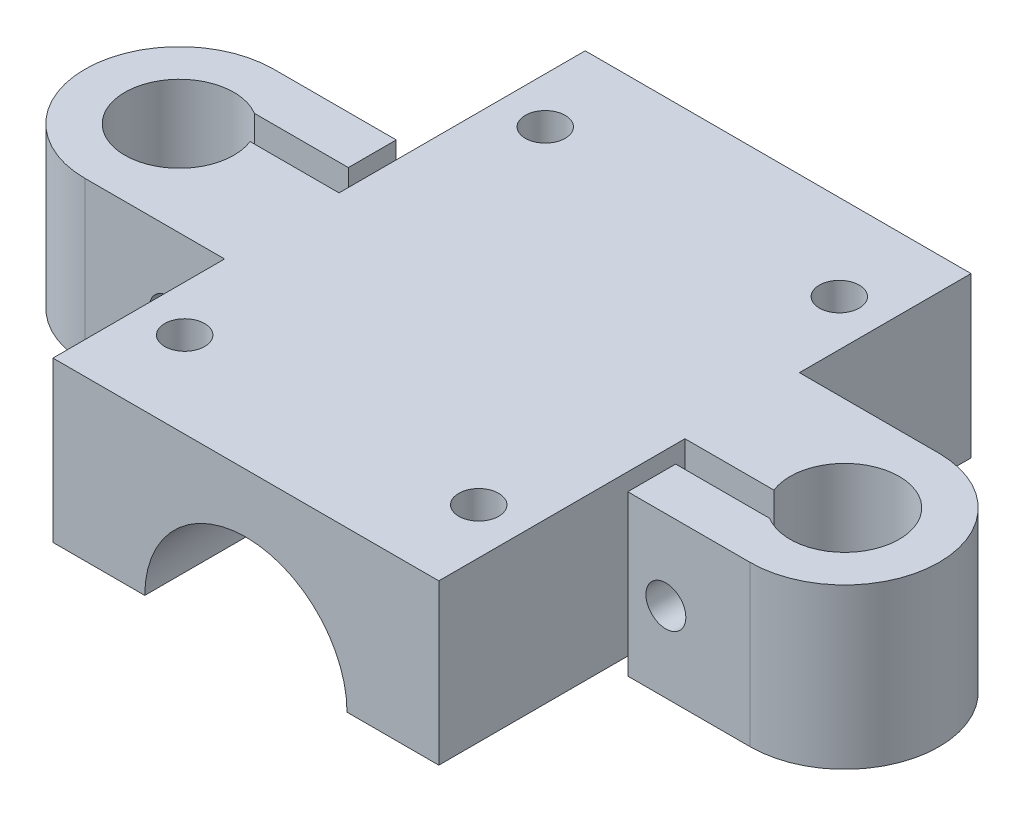
SolidWorks part; units mm, degrees
ref_plane "Front Plane" through (0, 0, 0) normal (1, 0, 0) x (0, 1, 0)
ref_plane "Top Plane" through (0, 0, 0) normal (0, 0, 1) x (0, 1, 0)
ref_plane "Right Plane" through (0, 0, 0) normal (0, 1, 0) x (-1, 0, 0)
sketch "Sketch1" plane through (0, 0, 0) normal (0, 0, 1) x (0, 1, 0)
  line L0 (0, -6.9) -> (0, -14.5) construction
  line L1 (0, 0) -> (12, 0)
  line L2 (0, 0) -> (0, -6.9)
  line L3 (0, -29) -> (12, -29)
  line L4 (12, 0) -> (12, -29)
  line L5 (6, -29) -> (6, 0) construction
  line L6 (0, -14.5) -> (12, -14.5) construction
  line L7 (0, -22.1) -> (0, -29)
  line L8 (0, -14.5) -> (0, -22.1) construction
  arc A0 (0, -22.1) -> (0, -6.9) centre (0, -14.5) ccw
  arc A1 (0, -6.9) -> (0, -22.1) centre (0, -14.5) ccw construction
  point P428 (6, -14.5)
  dimension "D3" = 15.2
  dimension "D1" = 29
  dimension "D2" = 12
extrude "Boss-Extrude1" add sketch "Sketch1" along normal blind 20 and the other way blind 20 contours A0 L7 L3 L4 L1 L2 region at (0.3138, 6, 0)
sketch "Sketch3" plane through (0, 12, 0) normal (0, 1, 0) x (-1, 0, 0)
  line L0 (0, 0) -> (-29, 0) construction
  line L1 (0, -20) -> (0, 20) construction
  line L2 (-29, -20) -> (-29, 20) construction
  line L3 (10.5, 0) -> (-39.5, 0) construction
  line L4 (10.5, -7.1) -> (-39.5, -7.1)
  line L5 (10.5, 7.1) -> (-39.5, 7.1)
  line L6 (-14.5, 20) -> (-14.5, -20) construction
  line L7 (0, 20) -> (-29, 20) construction
  line L8 (0, -20) -> (-29, -20) construction
  line L9 (1.3, -7.1) -> (1.3, -3.5)
  line L10 (1.3, -3.5) -> (8.3646, -3.5)
  line L11 (6.6842, -1.5) -> (0, -1.5)
  line L12 (0, -1.5) -> (0, -7.1)
  line L13 (0, -7.1) -> (1.3, -7.1)
  line L14 (-30.3, 7.1) -> (-30.3, 3.5)
  line L15 (-30.3, 3.5) -> (-37.3646, 3.5)
  line L16 (-35.6842, 1.5) -> (-29, 1.5)
  line L17 (-29, 1.5) -> (-29, 7.1)
  line L18 (-29, 7.1) -> (-30.3, 7.1)
  arc A0 (10.5, -7.1) -> (10.5, 7.1) centre (10.5, 0) ccw
  arc A1 (-39.5, 7.1) -> (-39.5, -7.1) centre (-39.5, 0) ccw
  arc A2 (-37.3646, 3.5) -> (-35.6842, 1.5) centre (-39.5, 0) ccw
  arc A3 (8.3646, -3.5) -> (6.6842, -1.5) centre (10.5, 0) ccw
  arc A4 (6.6842, -1.5) -> (8.3646, -3.5) centre (10.5, 0) ccw construction
  arc A5 (-35.6842, 1.5) -> (-37.3646, 3.5) centre (-39.5, 0) ccw construction
  point P9 (-14.5, 0)
  point P22 (-14.5, 0)
  line M6 (0, -20) -> (0, 20)
  line M8 (-29, 20) -> (-29, -20)
  dimension "D3" = 8.2
  dimension "D4" = 50
  dimension "D5" = 2
  dimension "D7" = 1.5
  dimension "D8" = 1.3
  dimension "D9" = 2
  dimension "D10" = 1.5
extrude "Boss-Extrude2" add sketch "Sketch3" against normal up to surface (12 mm away) contours A3 L10 L9 L4 A0 L5 L11 M6 | A2 L15 L14 L5 A1 L4 L16 M8 region at (-5.9, 12, -6.8739) region at (34.25, 12, -6.8739) up to face at (3.45, 0, 0)
sketch "Sketch4" plane through (0, 0, -1.5) normal (0, 0, -1) x (1, 0, 0)
  line L0 (-6.6842, -6) -> (0, -6) construction
  line L1 (-6.6842, 0) -> (-6.6842, -12) construction
  circle A0 centre (-4.1642, -6) radius 1.5
  dimension "screw_hole" = 3
  dimension "D1" = 2.52
extrude "Cut-Extrude1" cut sketch "Sketch4" against normal through all and the other way through all contours A0 L0 | L0 A0 region at (-4.1642, 5.3634, -1.5) region at (-4.1642, 6.6366, -1.5)
sketch "Sketch5" plane through (0, 0, 1.5) normal (0, 0, 1) x (1, 0, 0)
  line L0 (35.6842, 6) -> (29, 6) construction
  line L1 (35.6842, 0) -> (35.6842, 12) construction
  line L2 (29, 0) -> (29, 12) construction
  circle A0 centre (33.1642, 6) radius 1.5
  dimension "D2" = 2.52
extrude "Cut-Extrude2" cut sketch "Sketch5" against normal through all and the other way through all contours L0 A0 | A0 L0 region at (33.1642, 5.3634, 1.5) region at (33.1642, 6.6366, 1.5)
sketch "Sketch7" plane through (0, 0, 0) normal (0, -1, 0) x (1, 0, 0)
  line L0 (0, 20) -> (6.9, 7.1) construction
  line L1 (6.9, -20) -> (6.9, 20) construction
  line L2 (0, 7.1) -> (6.9, 20) construction
  line L3 (29, -7.1) -> (22.1, -20) construction
  line L4 (29, -20) -> (22.1, -7.1) construction
  line L5 (22.1, -20) -> (22.1, 20) construction
  line L6 (0, -20) -> (6.9, -7.1) construction
  line L7 (6.9, -20) -> (0, -7.1) construction
  line L9 (22.1, 20) -> (29, 7.1) construction
  line L10 (29, 1.5) -> (29, 20) construction
  line L11 (29, 20) -> (22.1, 7.1) construction
  line L12 (0, -20) -> (0, -1.5) construction
  circle A0 centre (3.45, 13.55) radius 1.5
  circle A1 centre (25.55, -13.55) radius 1.5
  circle A2 centre (25.55, 13.55) radius 1.5
  circle A3 centre (3.45, -13.55) radius 1.5
  dimension "D3" = 12.9
  dimension "D4" = 12.9
  dimension "x_hole_offset" = 12.9
  dimension "D6" = 12.9
extrude "Cut-Extrude3" cut sketch "Sketch7" against normal through all
equation "\"D2@Sketch3\"=\"D1@Sketch3\""
equation "\"D8@Sketch3\"=\"D6@Sketch3\""
equation "\"D9@Sketch3\"=\"D5@Sketch3\""
equation "\"D10@Sketch3\"=\"D7@Sketch3\""
equation "\"screw_hole\"= 3mm"
equation "\"offset\"= 2.52mm"
equation "\"screw_hole@Sketch4\"=\"screw_hole\""
equation "\"D1@Sketch4\"=\"offset\""
equation "\"D1@Sketch5\"=\"screw_hole\""
equation "\"D2@Sketch5\"=\"offset\""
equation "\"D1@Sketch7\"=\"screw_hole\""
equation "\"D4@Sketch7\"=\"D3@Sketch7\""
equation "\"y_length\" = 40mm"
equation "\"z_breadth\"= 29mm"
equation "\"D1@Boss-Extrude1\"=\"y_length\"/2"
equation "\"D2@Boss-Extrude1\"=\"y_length\"/2"
equation "\"D1@Sketch1\"=\"z_breadth\""
equation "\"lm8uu_bearing_dia\"= 15.2mm"
equation "\"D3@Sketch1\"= \"lm8uu_bearing_dia\""
